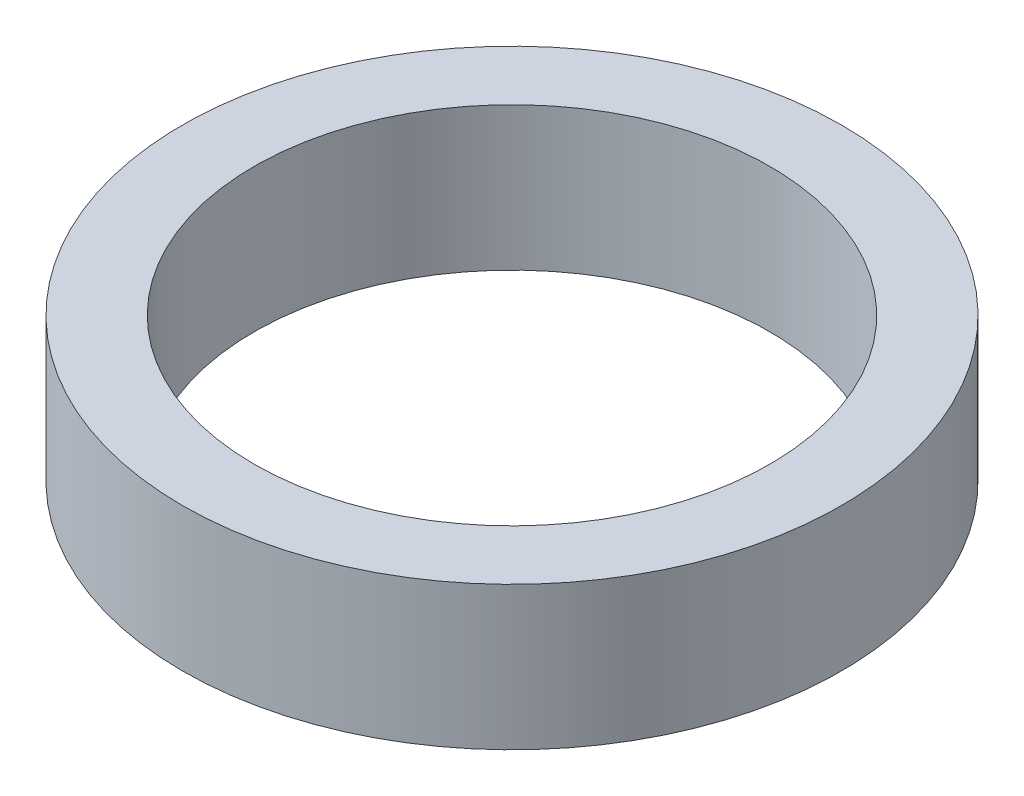
SolidWorks part; units mm, degrees
material "1023 Carbon Steel Sheet (SS)"
ref_plane "Front Plane" through (0, 0, 0) normal (0, 0, 1) x (1, 0, 0)
ref_plane "Top Plane" through (0, 0, 0) normal (0, 1, 0) x (1, 0, 0)
ref_plane "Right Plane" through (0, 0, 0) normal (1, 0, 0) x (0, 0, -1)
sketch "Sketch1" plane through (0, 0, 0) normal (0, 1, 0) x (1, 0, 0)
  circle A0 centre (0, 0) radius 29.21
  circle A1 centre (0, 0) radius 22.86
  dimension "D1" = 6.35
  dimension "D2" = 45.72
extrude "Boss-Extrude2" add sketch "Sketch1" along normal blind 12.7 contours A0 A1 region at (-28.3838, 0, 0)
sketch "Sketch2" plane through (0, 0, 0) normal (1, 0, 0) x (0, 0, -1)
  line L1 (0, 0) -> (0, 12.7)
  line L2 (29.21, 12.7) -> (-29.21, 12.7) construction
  line L6 (-29.21, 0) -> (29.21, 0) construction
  line L9 (-29.21, 0) -> (-22.86, 0) construction
  line L10 (-29.1459, 0) -> (-22.9241, 0)
  arc A2 (-29.1459, 0) -> (-22.9241, 0) centre (-26.035, -0.635) cw
  point P18 (-26.035, 0)
  point P19 (-26.035, 2.54)
  dimension "D1" = 3.175
  dimension "D2" = 2.54
revolve "Cut-Revolve1" cut sketch "Sketch2" angle 360 about L1
